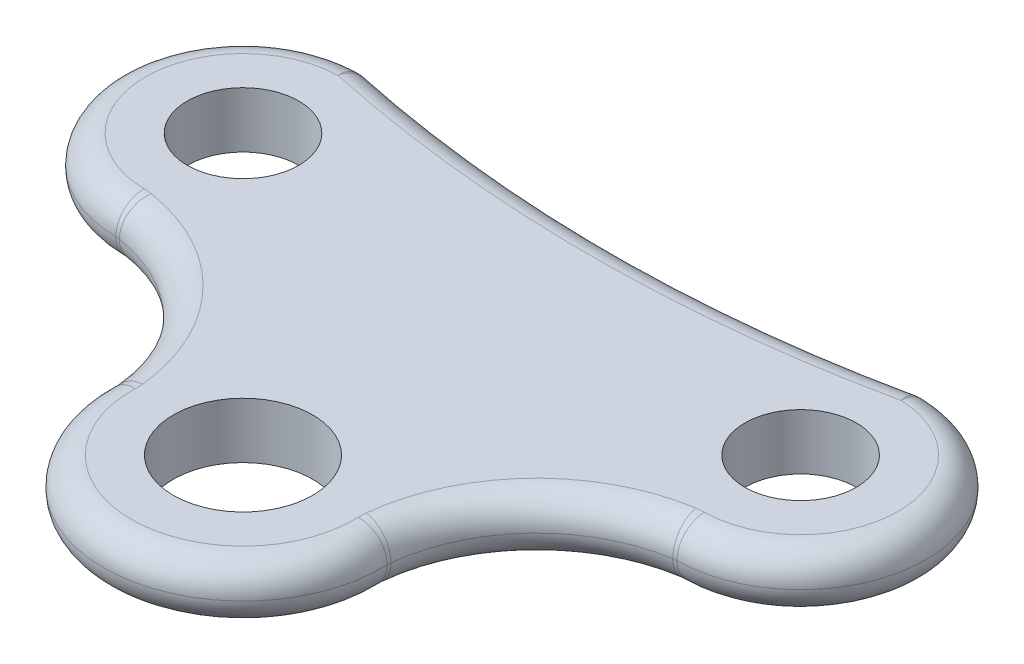
SolidWorks part; units mm, degrees
material "ABS PC"
ref_plane "Front Plane" through (0, 0, 0) normal (0, 0, 1) x (1, 0, 0)
ref_plane "Top Plane" through (0, 0, 0) normal (0, 1, 0) x (1, 0, 0)
ref_plane "Right Plane" through (0, 0, 0) normal (1, 0, 0) x (0, 0, -1)
sketch "Sketch1" plane through (0, 0, 0) normal (0, 1, 0) x (1, 0, 0)
  circle A0 centre (0, 0) radius 5
  circle A1 centre (-20, 20) radius 4
  circle A2 centre (20, 20) radius 4
  arc A3 (-20, 29) -> (-20, 11) centre (-20, 20) ccw
  arc A4 (-9.9894, 0.4603) -> (9.9894, 0.4603) centre (0, 0) ccw
  arc A5 (20, 11) -> (20, 29) centre (20, 20) ccw
  arc A6 (-9.9894, 0.4603) -> (-20, 11) centre (-21.6648, -0.6051) ccw
  arc A7 (9.9894, 0.4603) -> (20, 11) centre (21.6648, -0.6051) cw
  arc A8 (-20, 29) -> (20, 29) centre (0, 121.529) ccw
  circle A9 centre (-20, 20) radius 9 construction
  circle A10 centre (20, 20) radius 9 construction
  circle A11 centre (0, 0) radius 10 construction
  dimension "D1" = 8
  dimension "D2" = 10
  dimension "D3" = 8
  dimension "D4" = 20
  dimension "D5" = 20
  dimension "D6" = 20
  dimension "D7" = 20
extrude "Boss-Extrude1" add sketch "Sketch1" along normal blind 4
fillet "Fillet1" radius 2 12 edges at (-13.1641, 4, -7.4688) (-13.1641, 0, -7.4688) (13.1641, 4, -7.4688) (13.1641, 0, -7.4688) (-29, 4, -20) (-29, 0, -20) (0, 4, 10) (0, 0, 10) (29, 4, -20) (29, 0, -20) (0, 4, -26.8632) (0, 0, -26.8632)
